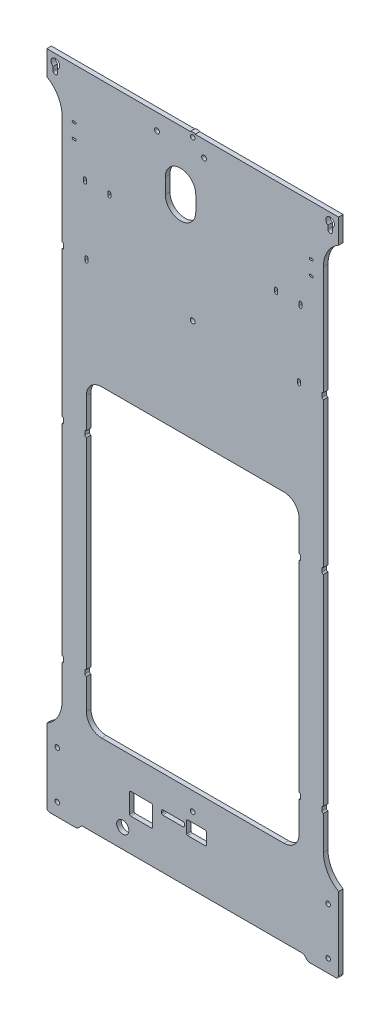
SolidWorks part; units mm, degrees
material "6061-T6 Black anodised"
ref_plane "Front Plane" through (0, 0, 0) normal (0, 0, 1) x (1, 0, 0)
ref_plane "Top Plane" through (0, 0, 0) normal (0, 1, 0) x (1, 0, 0)
ref_plane "Right Plane" through (0, 0, 0) normal (1, 0, 0) x (0, 0, -1)
sketch "Sketch1" plane through (0, 0, 0) normal (0, 0, 1) x (1, 0, 0)
  line L0 (89.02, 0) -> (-89.02, 0) construction
  line L1 (95.92, 394.5) -> (-95.92, 394.5)
  line L2 (95.92, 394.5) -> (95.92, -36.5)
  line L3 (72.92, -36.5) -> (-72.92, -36.5)
  line L4 (-95.92, 394.5) -> (-95.92, -36.5)
  line L5 (95.92, 394.5) -> (-95.92, -36.5) construction
  line L6 (95.92, -36.5) -> (-95.92, 394.5) construction
  line L7 (-90.52, -31) -> (-90.52, -28.5767) construction
  line L8 (-90.32, 384) -> (90.32, 384) construction
  line L9 (0, 384) -> (0, 0) construction
  line L10 (-87.52, -31) -> (-87.52, -28.5767) construction
  line L11 (-90.52, 0) -> (-90.52, 2.4233) construction
  line L12 (-87.52, 0) -> (-87.52, 2.4233) construction
  line L13 (87.52, -31) -> (87.52, -28.5767) construction
  line L14 (90.52, -31) -> (90.52, -28.5767) construction
  line L15 (87.52, 0) -> (87.52, 2.4233) construction
  line L16 (90.52, 0) -> (90.52, 2.4233) construction
  line L17 (88.82, 384) -> (88.82, 386.4233)
  line L18 (91.82, 384) -> (91.82, 386.4233)
  line L19 (-91.82, 384) -> (-91.82, 386.4233)
  line L20 (-88.82, 384) -> (-88.82, 386.4233)
  line L21 (95.92, -39.5) -> (75.92, -39.5)
  line L22 (75.92, -39.5) -> (72.92, -36.5)
  line L23 (-95.92, -39.5) -> (-75.92, -39.5)
  line L24 (-75.92, -39.5) -> (-72.92, -36.5)
  line L25 (-95.92, -36.5) -> (-95.92, -39.5)
  line L26 (95.92, -36.5) -> (95.92, -39.5)
  arc A0 (-90.52, 0) -> (-87.52, 0) centre (-89.02, 0) ccw
  arc A1 (87.52, 0) -> (90.52, 0) centre (89.02, 0) ccw
  arc A2 (-90.52, -31) -> (-87.52, -31) centre (-89.02, -31) ccw
  arc A4 (-91.82, 384) -> (-88.82, 384) centre (-90.32, 384) ccw
  arc A5 (88.82, 384) -> (91.82, 384) centre (90.32, 384) ccw
  arc A6 (-87.52, -28.5767) -> (-90.52, -28.5767) centre (-89.02, -26.1534) ccw construction
  circle A7 centre (-89.02, -31) radius 2.85 construction
  arc A8 (-87.52, 2.4233) -> (-90.52, 2.4233) centre (-89.02, 4.8466) ccw construction
  circle A9 centre (-89.02, 0) radius 2.85 construction
  arc A10 (90.52, -28.5767) -> (87.52, -28.5767) centre (89.02, -26.1534) ccw construction
  circle A11 centre (89.02, -31) radius 2.85 construction
  arc A12 (90.52, 2.4233) -> (87.52, 2.4233) centre (89.02, 4.8466) ccw construction
  circle A13 centre (89.02, 0) radius 2.85 construction
  arc A14 (91.82, 386.4233) -> (88.82, 386.4233) centre (90.32, 388.8466) ccw
  circle A15 centre (90.32, 384) radius 2.85 construction
  arc A16 (-88.82, 386.4233) -> (-91.82, 386.4233) centre (-90.32, 388.8466) ccw
  circle A17 centre (-90.32, 384) radius 2.85 construction
  circle A18 centre (89.02, -31) radius 1.5
  arc A19 (90.52, 0) -> (87.52, 0) centre (89.02, 0) ccw
  arc A20 (-90.52, -31) -> (-87.52, -31) centre (-89.02, -31) cw
  arc A21 (-90.52, 0) -> (-87.52, 0) centre (-89.02, 0) cw
  point P0 (0, 179)
  point P59 (-81.27, 0)
  dimension "D4" = 3
  dimension "D9" = 5.7
  dimension "D7" = 5.6
  dimension "D1" = 191.84
  dimension "D2" = 431
  dimension "D3" = 6.9
  dimension "D5" = 31
  dimension "D6" = 5.5
  dimension "D8" = 10.5
  dimension "D10" = 3
  dimension "D11" = 20
  dimension "D12" = 45
extrude "Boss-Extrude1" add sketch "Sketch1" along normal blind 3
sketch "Sketch2" plane through (0, 0, 3) normal (0, 0, 1) x (1, 0, 0)
  line L0 (-95.92, 394.5) -> (-95.92, -39.5) construction
  line L1 (-95.92, 10.5) -> (-85.92, 10.5)
  line L2 (-95.92, 10.5) -> (-95.92, 378.5)
  line L3 (-95.92, 378.5) -> (-85.92, 378.5)
  line L4 (-85.92, 10.5) -> (-85.92, 378.5)
  line L5 (95.92, -39.5) -> (95.92, 394.5) construction
  line L6 (95.92, 10.5) -> (85.92, 10.5)
  line L7 (95.92, 10.5) -> (95.92, 378.5)
  line L8 (95.92, 378.5) -> (85.92, 378.5)
  line L9 (85.92, 10.5) -> (85.92, 378.5)
  line L10 (95.92, 394.5) -> (-95.92, 394.5) construction
  line L11 (-72.92, -36.5) -> (72.92, -36.5) construction
  dimension "D1" = 16
  dimension "D2" = 47
  dimension "D3" = 10
extrude "Cut-Extrude1" cut sketch "Sketch2" against normal through all
fillet "Fillet1" radius 20 4 edges at (85.92, 10.5, 1.5) (-85.92, 10.5, 1.5) (85.92, 378.5, 1.5) (-85.92, 378.5, 1.5)
sketch "Sketch3" plane through (0, 0, 3) normal (0, 0, 1) x (1, 0, 0)
  line L0 (-72.92, -36.5) -> (72.92, -36.5) construction
  line L1 (95.92, 394.5) -> (-95.92, 394.5) construction
  circle A0 centre (0, 8) radius 1.5
  circle A2 centre (0, 392) radius 1.5
  dimension "D2" = 2.5
  dimension "D3" = 3
  dimension "D1" = 44.5
extrude "Cut-Extrude2" cut sketch "Sketch3" against normal through all
sketch "Sketch4" plane through (0, 0, 3) normal (0, 0, 1) x (1, 0, 0)
  line L0 (-85.92, 27.8205) -> (-85.92, 361.1795) construction
  line L1 (-69.92, 220) -> (69.92, 220)
  line L2 (-69.92, 220) -> (-69.92, 20)
  line L3 (-69.92, 20) -> (69.92, 20)
  line L4 (69.92, 220) -> (69.92, 20)
  line L5 (-69.92, 220) -> (69.92, 20) construction
  line L6 (-69.92, 20) -> (69.92, 220) construction
  circle A0 centre (0, 8) radius 1.5 construction
  point P0 (0, 120)
  dimension "D1" = 16
  dimension "D2" = 12
  dimension "D3" = 200
extrude "Cut-Extrude3" cut sketch "Sketch4" against normal through all
fillet "Fillet2" radius 10 4 edges at (69.92, 220, 1.5) (-69.92, 220, 1.5) (69.92, 20, 1.5) (-69.92, 20, 1.5)
sketch "Sketch5" plane through (0, 0, 3) normal (0, 0, 1) x (1, 0, 0)
  line L0 (-46, 8.2274) -> (-46, -20.9664) construction
  line L6 (-41.5, -0.8) -> (-26.5, -0.8)
  line L7 (-41.5, -0.8) -> (-41.5, -14.9)
  line L8 (-41.5, -14.9) -> (-26.5, -14.9)
  line L9 (-26.5, -0.8) -> (-26.5, -14.9)
  line L10 (-20.5, -0.8) -> (-5.5, -0.8)
  line L11 (-20.5, -0.8) -> (-20.5, -3.8)
  line L12 (-20.5, -3.8) -> (-5.5, -3.8)
  line L13 (-5.5, -0.8) -> (-5.5, -3.8)
  line L14 (-4, 1.7) -> (9, 1.7)
  line L15 (-4, 1.7) -> (-4, -7.3)
  line L16 (-4, -7.3) -> (9, -7.3)
  line L17 (9, 1.7) -> (9, -7.3)
  circle A1 centre (0, 8) radius 1.5 construction
  dimension "D3" = 2.5
  dimension "D2" = 8.8
  dimension "D5" = 46
  dimension "D6" = 4.5
  dimension "D7" = 15
  dimension "D8" = 25.5
  dimension "D9" = 15
  dimension "D10" = 42
  dimension "D11" = 13
  dimension "D12" = 14.1
  dimension "D13" = 3
  dimension "D14" = 9
extrude "Cut-Extrude4" cut sketch "Sketch5" against normal through all
fillet "Fillet3" radius 0.8 12 edges at (9, -7.3, 1.5) (9, 1.7, 1.5) (-4, 1.7, 1.5) (-4, -7.3, 1.5) (-5.5, -3.8, 1.5) (-5.5, -0.8, 1.5) (-20.5, -0.8, 1.5) (-20.5, -3.8, 1.5) (-26.5, -14.9, 1.5) (-26.5, -0.8, 1.5) (-41.5, -0.8, 1.5) (-41.5, -14.9, 1.5)
sketch "Sketch6" plane through (0, 0, 3) normal (0, 0, 1) x (1, 0, 0)
  circle A0 centre (-46, -23.8) radius 4
  circle A1 centre (0, 8) radius 1.5 construction
  dimension "D2" = 8
  dimension "D3" = 31.8
  dimension "D1" = 46
extrude "Cut-Extrude5" cut sketch "Sketch6" against normal through all
sketch "Sketch7" plane through (0, 0, 3) normal (0, 0, 1) x (1, 0, 0)
  line L0 (0, -35.055) -> (-4.8534, -39.9081)
  line L1 (6.0015, -39.9081) -> (0.8516, -35.055)
  line L2 (-7.2622, -33.0882) -> (7.8165, -33.0882)
  line L3 (8.077, -32.9782) -> (11.0039, -30.0512)
  line L4 (10.2253, -29.347) -> (-7.2622, -29.347)
  line L5 (-14.4113, -36.4965) -> (-14.4098, -53.9837)
  line L6 (-13.7057, -54.7607) -> (-10.7801, -51.8338)
  line L7 (-10.6686, -51.5749) -> (-10.67, -36.4965)
  line L8 (8.1139, -55.2833) -> (-6.9645, -55.2833)
  line L9 (-7.2249, -55.3948) -> (-10.1519, -58.3217)
  line L10 (-9.3733, -59.0259) -> (8.1139, -59.0259)
  line L11 (15.2633, -51.8752) -> (15.2619, -34.3893)
  line L12 (14.5577, -33.6121) -> (11.6308, -36.5391)
  line L13 (11.5207, -36.798) -> (11.5218, -51.8752)
  spline S0 degree 3 poles (0.4439, -34.8701) (0.3912, -34.8752) (0.2828, -34.8857) (0.1286, -34.9495) (0.0426, -35.02) (0, -35.055) knots 0 0 0 0 0.322338 0.663828 1 1 1 1
  spline S1 degree 3 poles (-4.8534, -39.9081) (-4.8579, -39.9123) (-4.8667, -39.9205) (-4.8791, -39.9329) (-5.3375, -40.4392) (-6.231, -41.4846) (-7.3312, -43.289) (-7.8887, -46.1117) (-6.8483, -49.6491) (-3.8783, -52.5981) (0.2577, -53.8719) (4.5569, -52.8137) (7.7118, -49.6441) (8.7217, -46.1226) (8.2109, -43.3277) (7.2971, -41.454) (6.4234, -40.4116) (6.0015, -39.9081) knots 0 0 0 0 0.000489 0.000958 0.001407 0.055151 0.111018 0.168413 0.280621 0.389777 0.490762 0.614387 0.723194 0.83533 0.891393 0.947551 1 1 1 1
  spline S2 degree 3 poles (0.8516, -35.055) (0.8125, -35.0211) (0.7352, -34.9541) (0.5954, -34.8849) (0.4944, -34.875) (0.4439, -34.8701) knots 0 0 0 0 0.338885 0.669777 1 1 1 1
  spline S3 degree 3 poles (7.8165, -33.0882) (7.8386, -33.0865) (7.882, -33.0833) (7.9472, -33.0756) (7.9964, -33.0496) (8.0324, -33.0241) (8.0557, -33.0007) (8.07, -32.9856) (8.077, -32.9782) knots 0 0 0 0 0.227493 0.445972 0.663373 0.787115 0.896006 1 1 1 1
  spline S4 degree 3 poles (11.0039, -30.0512) (11.0329, -30.0119) (11.0909, -29.9332) (11.1149, -29.785) (11.0877, -29.6491) (11.0204, -29.5396) (10.9299, -29.4607) (10.7969, -29.4113) (10.6368, -29.379) (10.4517, -29.3457) (10.3213, -29.3482) (10.25, -29.3467) (10.2377, -29.3461) (10.2294, -29.3467) (10.2253, -29.347) knots 0 0 0 0 0.104345 0.208931 0.313565 0.397995 0.482811 0.567894 0.701187 0.836715 0.973247 0.982163 0.991064 1 1 1 1
  spline S5 degree 3 poles (-7.2622, -29.347) (-8.5111, -29.5465) (-10.9772, -29.9405) (-13.8177, -32.781) (-14.2117, -35.2473) (-14.4113, -36.4965) knots 0 0 0 0 0.336154 0.663772 1 1 1 1
  spline S6 degree 3 poles (-14.4098, -53.9837) (-14.4101, -53.9877) (-14.4107, -53.9955) (-14.4101, -54.0074) (-14.4085, -54.0786) (-14.4116, -54.2092) (-14.3778, -54.3947) (-14.348, -54.5555) (-14.2965, -54.6876) (-14.2178, -54.7779) (-14.1086, -54.8459) (-13.9724, -54.8732) (-13.8239, -54.8488) (-13.7451, -54.7901) (-13.7057, -54.7607) knots 0 0 0 0 0.008622 0.017031 0.025643 0.162638 0.298245 0.431901 0.516392 0.601007 0.685957 0.790142 0.895037 1 1 1 1
  spline S7 degree 3 poles (-10.7801, -51.8338) (-10.7711, -51.8245) (-10.7536, -51.8064) (-10.7264, -51.7794) (-10.6977, -51.7438) (-10.6778, -51.6947) (-10.6682, -51.6355) (-10.6685, -51.5956) (-10.6686, -51.5749) knots 0 0 0 0 0.131285 0.25763 0.390972 0.594165 0.788898 1 1 1 1
  spline S8 degree 3 poles (-10.67, -36.4965) (-10.5818, -35.8926) (-10.4093, -34.7122) (-9.0474, -33.3492) (-7.8666, -33.1766) (-7.2622, -33.0882) knots 0 0 0 0 0.33841 0.661392 1 1 1 1
  spline S9 degree 3 poles (-6.9645, -55.2833) (-6.9836, -55.284) (-7.0187, -55.2854) (-7.0727, -55.2938) (-7.117, -55.3142) (-7.157, -55.3379) (-7.1915, -55.3639) (-7.2134, -55.3842) (-7.2249, -55.3948) knots 0 0 0 0 0.196746 0.361608 0.557262 0.692766 0.839563 1 1 1 1
  spline S10 degree 3 poles (-10.1519, -58.3217) (-10.1809, -58.361) (-10.2389, -58.4397) (-10.2629, -58.5879) (-10.2357, -58.7239) (-10.1681, -58.8333) (-10.0777, -58.912) (-9.9452, -58.9619) (-9.7851, -58.9945) (-9.6, -59.0248) (-9.4695, -59.0303) (-9.3981, -59.025) (-9.3857, -59.0257) (-9.3774, -59.0258) (-9.3733, -59.0259) knots 0 0 0 0 0.104385 0.20895 0.313569 0.398093 0.483012 0.567612 0.700915 0.836485 0.973043 0.982112 0.991066 1 1 1 1
  spline S11 degree 3 poles (8.1139, -59.0259) (9.3629, -58.8263) (11.8293, -58.432) (14.6704, -55.5912) (15.064, -53.1244) (15.2633, -51.8752) knots 0 0 0 0 0.336157 0.663806 1 1 1 1
  spline S12 degree 3 poles (15.2619, -34.3893) (15.2622, -34.3852) (15.2628, -34.3769) (15.2621, -34.3644) (15.2606, -34.293) (15.2632, -34.1626) (15.2298, -33.9775) (15.198, -33.8174) (15.148, -33.6849) (15.0694, -33.5945) (14.9599, -33.5269) (14.8239, -33.4997) (14.6754, -33.5241) (14.597, -33.5828) (14.5577, -33.6121) knots 0 0 0 0 0.008953 0.017947 0.027021 0.163491 0.298949 0.432165 0.516776 0.601601 0.686035 0.790672 0.895263 1 1 1 1
  spline S13 degree 3 poles (11.6308, -36.5391) (11.6212, -36.5483) (11.6023, -36.5664) (11.5737, -36.5942) (11.5433, -36.6274) (11.5265, -36.6769) (11.5219, -36.7355) (11.5211, -36.7763) (11.5207, -36.798) knots 0 0 0 0 0.134582 0.264928 0.404991 0.586048 0.77989 1 1 1 1
  spline S14 degree 3 poles (11.5218, -51.8752) (11.4339, -52.4792) (11.262, -53.6599) (9.8992, -55.0226) (8.7183, -55.195) (8.1139, -55.2833) knots 0 0 0 0 0.338406 0.661372 1 1 1 1
extrude "Cut-Extrude6" [suppressed] cut sketch "Sketch7" against normal through all
sketch "Sketch8" plane through (0, 0, 3) normal (0, 0, 1) x (1, 0, 0)
  line L0 (-13.1975, 364.095) -> (13.1975, 364.095) construction
  line L1 (-15.5, 383.9) -> (15.5, 383.9) construction
  line L2 (-15.5, 383.9) -> (-15.5, 352.9) construction
  line L3 (-15.5, 352.9) -> (15.5, 352.9) construction
  line L4 (15.5, 383.9) -> (15.5, 352.9) construction
  line L5 (-15.5, 383.9) -> (15.5, 352.9) construction
  line L6 (-15.5, 352.9) -> (15.5, 383.9) construction
  line L7 (-8, 350.4) -> (-8, 360.4) construction
  line L8 (-21, 347.4) -> (-21, 389.4) construction
  line L9 (-21, 389.4) -> (21, 389.4) construction
  line L10 (21, 347.4) -> (21, 389.4) construction
  line L11 (-21, 347.4) -> (21, 389.4) construction
  line L12 (-21, 389.4) -> (21, 347.4) construction
  line L13 (0, 368.4) -> (0, 392) construction
  line L15 (-18, 350.4) -> (-18, 360.4)
  line L16 (2, 350.4) -> (2, 360.4)
  line L17 (0, 368.4) -> (0, 364.095) construction
  line L23 (59.92, 220) -> (-59.92, 220) construction
  line L32 (1.5, 368.4) -> (-1.5, 368.4) construction
  line L35 (-23.5, 383.9) -> (7.5, 383.9) construction
  circle A0 centre (-15.5, 383.9) radius 1.6 construction
  circle A1 centre (15.5, 383.9) radius 1.6 construction
  circle A2 centre (15.5, 352.9) radius 1.6 construction
  circle A3 centre (-15.5, 352.9) radius 1.6 construction
  circle A4 centre (0, 392) radius 1.5 construction
  arc A6 (-18, 350.4) -> (2, 350.4) centre (-8, 350.4) ccw
  arc A7 (2, 360.4) -> (-18, 360.4) centre (-8, 360.4) ccw
  circle A8 centre (0, 287.5) radius 67.5 construction
  circle A9 centre (0, 287.5) radius 1.6
  circle A13 centre (7.5, 383.9) radius 1.6
  circle A14 centre (-23.5, 383.9) radius 1.6
  point P0 (0, 368.4)
  point P9 (0, 368.4)
  point P24 (-8, 355.4)
  point P56 (20, 368.4)
  dimension "D2" = 3.2
  dimension "D11" = 10
  dimension "D14" = 3.2
  dimension "D15" = 135
  dimension "D10" = 10
  dimension "D1" = 31
  dimension "D4" = 2.6
  dimension "D6" = 4.305
  dimension "D7" = 23.6
  dimension "D12" = 15.5
  dimension "D13" = 23.5
  dimension "D19" = 6
  dimension "D20" = 3
extrude "Cut-Extrude7" cut sketch "Sketch8" against normal through all
sketch "Sketch9" plane through (0, 0, 3) normal (0, 0, 1) x (1, 0, 0)
  line L0 (95.92, 394.5) -> (-95.92, 394.5) construction
  line L1 (-1.6583, 394.5) -> (1.6583, 394.5)
  arc A0 (1.6583, 394.5) -> (-1.6583, 394.5) centre (0, 392) ccw
  dimension "D1" = 3
extrude "Boss-Extrude2" add sketch "Sketch9" against normal up to surface (3 mm away) up to face at (-21.9, 383.9, 0)
sketch "Sketch10" plane through (0, 0, 3) normal (0, 0, 1) x (1, 0, 0)
  line L0 (0, 392) -> (0, 361.5) construction
  line L1 (-77.92, 361.5) -> (77.92, 361.5) construction
  line L2 (-85.92, 27.8205) -> (-85.92, 361.1795) construction
  line L3 (-1.6583, 394.5) -> (-95.92, 394.5) construction
  line L4 (-77.92, 361.5) -> (-47.92, 361.5) construction
  line L5 (-78.57, 361.5) -> (-77.27, 361.5) construction
  line L6 (-78.57, 362.15) -> (-77.27, 362.15)
  line L7 (-78.57, 360.85) -> (-77.27, 360.85)
  line L8 (-78.57, 352) -> (-77.27, 352) construction
  line L9 (-78.57, 352.65) -> (-77.27, 352.65)
  line L10 (-78.57, 351.35) -> (-77.27, 351.35)
  line L17 (77.27, 361.5) -> (78.57, 361.5) construction
  line L18 (77.27, 362.15) -> (78.57, 362.15)
  line L19 (77.27, 360.85) -> (78.57, 360.85)
  line L20 (77.27, 352) -> (78.57, 352) construction
  line L21 (77.27, 352.65) -> (78.57, 352.65)
  line L22 (77.27, 351.35) -> (78.57, 351.35)
  circle A0 centre (-77.92, 361.5) radius 0.65 construction
  circle A1 centre (-77.92, 352) radius 0.65 construction
  circle A2 centre (77.92, 361.5) radius 0.65 construction
  circle A3 centre (77.92, 352) radius 0.65 construction
  arc A6 (-78.57, 362.15) -> (-78.57, 360.85) centre (-78.57, 361.5) ccw
  arc A7 (-77.27, 360.85) -> (-77.27, 362.15) centre (-77.27, 361.5) ccw
  arc A8 (-78.57, 352.65) -> (-78.57, 351.35) centre (-78.57, 352) ccw
  arc A9 (-77.27, 351.35) -> (-77.27, 352.65) centre (-77.27, 352) ccw
  arc A14 (77.27, 362.15) -> (77.27, 360.85) centre (77.27, 361.5) ccw
  arc A15 (78.57, 360.85) -> (78.57, 362.15) centre (78.57, 361.5) ccw
  arc A16 (77.27, 352.65) -> (77.27, 351.35) centre (77.27, 352) ccw
  arc A17 (78.57, 351.35) -> (78.57, 352.65) centre (78.57, 352) ccw
  point P24 (-77.92, 361.5)
  point P29 (-77.92, 352)
  point P50 (77.92, 361.5)
  point P57 (77.92, 352)
  dimension "D2" = 1.3
  dimension "D1" = 9.5
  dimension "D3" = 8
  dimension "D4" = 33
extrude "Cut-Extrude8" cut sketch "Sketch10" against normal through all
sketch "Sketch11" plane through (0, 0, 3) normal (0, 0, 1) x (1, 0, 0)
  line L0 (85.92, 189) -> (85.92, 187) construction
  line L1 (86.92, 189) -> (86.92, 187)
  line L2 (84.92, 189) -> (84.92, 187)
  line L3 (0, 0) -> (0, 406.4665) construction
  line L4 (69.92, 189) -> (69.92, 187) construction
  line L5 (70.92, 189) -> (70.92, 187)
  line L6 (-85.92, 53) -> (-85.92, 51) construction
  line L7 (68.92, 189) -> (68.92, 187)
  line L8 (85.92, 288.5) -> (85.92, 286.5) construction
  line L9 (86.92, 288.5) -> (86.92, 286.5)
  line L10 (84.92, 288.5) -> (84.92, 286.5)
  line L11 (69.92, 288.5) -> (69.92, 286.5) construction
  line L12 (70.92, 288.5) -> (70.92, 286.5)
  line L13 (68.92, 288.5) -> (68.92, 286.5)
  line L14 (59.92, 220) -> (-59.92, 220) construction
  line L15 (85.92, 53) -> (85.92, 51) construction
  line L16 (86.92, 53) -> (86.92, 51)
  line L17 (84.92, 53) -> (84.92, 51)
  line L18 (69.92, 53) -> (69.92, 51) construction
  line L19 (70.92, 53) -> (70.92, 51)
  line L20 (68.92, 53) -> (68.92, 51)
  line L21 (-86.92, 53) -> (-86.92, 51)
  line L22 (85.92, 189) -> (69.92, 189) construction
  line L23 (85.92, 361.1795) -> (85.92, 27.8205) construction
  line L24 (-84.92, 53) -> (-84.92, 51)
  line L25 (-69.92, 53) -> (-69.92, 51) construction
  line L26 (-70.92, 53) -> (-70.92, 51)
  line L27 (-59.92, 20) -> (59.92, 20) construction
  line L28 (-68.92, 53) -> (-68.92, 51)
  line L29 (-85.92, 189) -> (-85.92, 187) construction
  line L30 (-86.92, 189) -> (-86.92, 187)
  line L31 (-84.92, 189) -> (-84.92, 187)
  line L32 (-69.92, 189) -> (-69.92, 187) construction
  line L33 (-70.92, 189) -> (-70.92, 187)
  line L34 (-68.92, 189) -> (-68.92, 187)
  line L35 (-85.92, 288.5) -> (-85.92, 286.5) construction
  line L36 (-86.92, 288.5) -> (-86.92, 286.5)
  line L37 (-84.92, 288.5) -> (-84.92, 286.5)
  line L38 (-69.92, 288.5) -> (-69.92, 286.5) construction
  line L39 (-70.92, 288.5) -> (-70.92, 286.5)
  line L40 (-68.92, 288.5) -> (-68.92, 286.5)
  line L41 (70.8127, 333) -> (70.8127, 331) construction
  line L42 (71.8127, 333) -> (71.8127, 331)
  line L43 (69.8127, 333) -> (69.8127, 331)
  line L44 (54.8127, 333) -> (54.8127, 331) construction
  line L45 (55.8127, 333) -> (55.8127, 331)
  line L46 (53.8127, 333) -> (53.8127, 331)
  line L47 (-70.8127, 333) -> (-70.8127, 331) construction
  line L48 (-71.8127, 333) -> (-71.8127, 331)
  line L49 (-69.8127, 333) -> (-69.8127, 331)
  line L50 (-54.8127, 333) -> (-54.8127, 331) construction
  line L51 (-55.8127, 333) -> (-55.8127, 331)
  line L52 (-53.8127, 333) -> (-53.8127, 331)
  arc A0 (86.92, 189) -> (84.92, 189) centre (85.92, 189) ccw
  arc A1 (84.92, 187) -> (86.92, 187) centre (85.92, 187) ccw
  arc A2 (70.92, 189) -> (68.92, 189) centre (69.92, 189) ccw
  arc A3 (68.92, 187) -> (70.92, 187) centre (69.92, 187) ccw
  arc A4 (86.92, 288.5) -> (84.92, 288.5) centre (85.92, 288.5) ccw
  arc A5 (84.92, 286.5) -> (86.92, 286.5) centre (85.92, 286.5) ccw
  arc A6 (70.92, 288.5) -> (68.92, 288.5) centre (69.92, 288.5) ccw
  arc A7 (68.92, 286.5) -> (70.92, 286.5) centre (69.92, 286.5) ccw
  arc A8 (86.92, 53) -> (84.92, 53) centre (85.92, 53) ccw
  arc A9 (84.92, 51) -> (86.92, 51) centre (85.92, 51) ccw
  arc A10 (70.92, 53) -> (68.92, 53) centre (69.92, 53) ccw
  arc A11 (68.92, 51) -> (70.92, 51) centre (69.92, 51) ccw
  arc A12 (-86.92, 53) -> (-84.92, 53) centre (-85.92, 53) cw
  arc A13 (-84.92, 51) -> (-86.92, 51) centre (-85.92, 51) cw
  arc A14 (-70.92, 53) -> (-68.92, 53) centre (-69.92, 53) cw
  arc A15 (-68.92, 51) -> (-70.92, 51) centre (-69.92, 51) cw
  arc A16 (-86.92, 189) -> (-84.92, 189) centre (-85.92, 189) cw
  arc A17 (-84.92, 187) -> (-86.92, 187) centre (-85.92, 187) cw
  arc A18 (-70.92, 189) -> (-68.92, 189) centre (-69.92, 189) cw
  arc A19 (-68.92, 187) -> (-70.92, 187) centre (-69.92, 187) cw
  arc A20 (-86.92, 288.5) -> (-84.92, 288.5) centre (-85.92, 288.5) cw
  arc A21 (-84.92, 286.5) -> (-86.92, 286.5) centre (-85.92, 286.5) cw
  arc A22 (-70.92, 288.5) -> (-68.92, 288.5) centre (-69.92, 288.5) cw
  arc A23 (-68.92, 286.5) -> (-70.92, 286.5) centre (-69.92, 286.5) cw
  arc A24 (71.8127, 333) -> (69.8127, 333) centre (70.8127, 333) ccw
  arc A25 (69.8127, 331) -> (71.8127, 331) centre (70.8127, 331) ccw
  arc A26 (55.8127, 333) -> (53.8127, 333) centre (54.8127, 333) ccw
  arc A27 (53.8127, 331) -> (55.8127, 331) centre (54.8127, 331) ccw
  arc A28 (77.27, 352.65) -> (77.27, 351.35) centre (77.27, 352) ccw construction
  arc A29 (-71.8127, 333) -> (-69.8127, 333) centre (-70.8127, 333) cw
  arc A30 (-69.8127, 331) -> (-71.8127, 331) centre (-70.8127, 331) cw
  arc A31 (-55.8127, 333) -> (-53.8127, 333) centre (-54.8127, 333) cw
  arc A32 (-53.8127, 331) -> (-55.8127, 331) centre (-54.8127, 331) cw
  point P2 (85.92, 188)
  point P12 (69.92, 188)
  point P19 (85.92, 287.5)
  point P26 (69.92, 287.5)
  point P35 (85.92, 52)
  point P42 (69.92, 52)
  point P49 (0, 287.5)
  point P58 (-85.92, 52)
  point P65 (-69.92, 52)
  point P72 (-85.92, 188)
  point P79 (-69.92, 188)
  point P86 (-85.92, 287.5)
  point P93 (-69.92, 287.5)
  point P100 (70.8127, 332)
  point P105 (54.8127, 332)
  point P112 (76.62, 352)
  point P118 (-70.8127, 332)
  point P125 (-54.8127, 332)
  dimension "D6" = 32
  dimension "D1" = 2
  dimension "D2" = 2
  dimension "D3" = 32
  dimension "D4" = 16
  dimension "D5" = 2
  dimension "D7" = 20
  dimension "D8" = 16
extrude "Cut-Extrude9" cut sketch "Sketch11" against normal through all
fillet "Fillet5" radius 2 6 edges at (72.92, -36.5, 1.5) (75.92, -39.5, 1.5) (95.92, -39.5, 1.5) (-72.92, -36.5, 1.5) (-75.92, -39.5, 1.5) (-95.92, -39.5, 1.5)
sketch "Sketch12" plane through (0, 0, 3) normal (0, 0, 1) x (1, 0, 0)
  line L0 (-88.02, 7.7) -> (-81.17, 7.7)
  line L1 (-88.02, -23.3) -> (-81.17, -23.3)
  line L2 (-88.02, 7.7) -> (-88.02, -3.5)
  line L3 (-88.02, -3.5) -> (-81.17, -3.5)
  line L4 (-88.02, -23.3) -> (-88.02, -34.5)
  line L5 (-81.17, 7.7) -> (-81.17, -3.5)
  line L6 (-95.92, 10.5) -> (-95.92, -37.5) construction
  line L7 (-88.02, -34.5) -> (-81.17, -34.5)
  line L8 (-81.17, -23.3) -> (-81.17, -34.5)
  line L9 (-81.27, 0) -> (-81.27, -31) construction
  circle A0 centre (0, 8) radius 1.5 construction
  point P8 (-81.27, 0)
  point P15 (-81.27, -31)
  dimension "D5" = 8
  dimension "D1" = 3.5
  dimension "D2" = 6.85
  dimension "D3" = 7.9
  dimension "D4" = 11.2
  dimension "D7" = 31
  dimension "D6" = 2
extrude "Cut-Extrude10" [suppressed] cut sketch "Sketch12" against normal through all
chamfer "Chamfer1" [suppressed] distance 3 angle 10
mirror "Mirror1" [suppressed] about plane through (0, 0, 0) normal (1, 0, 0)
